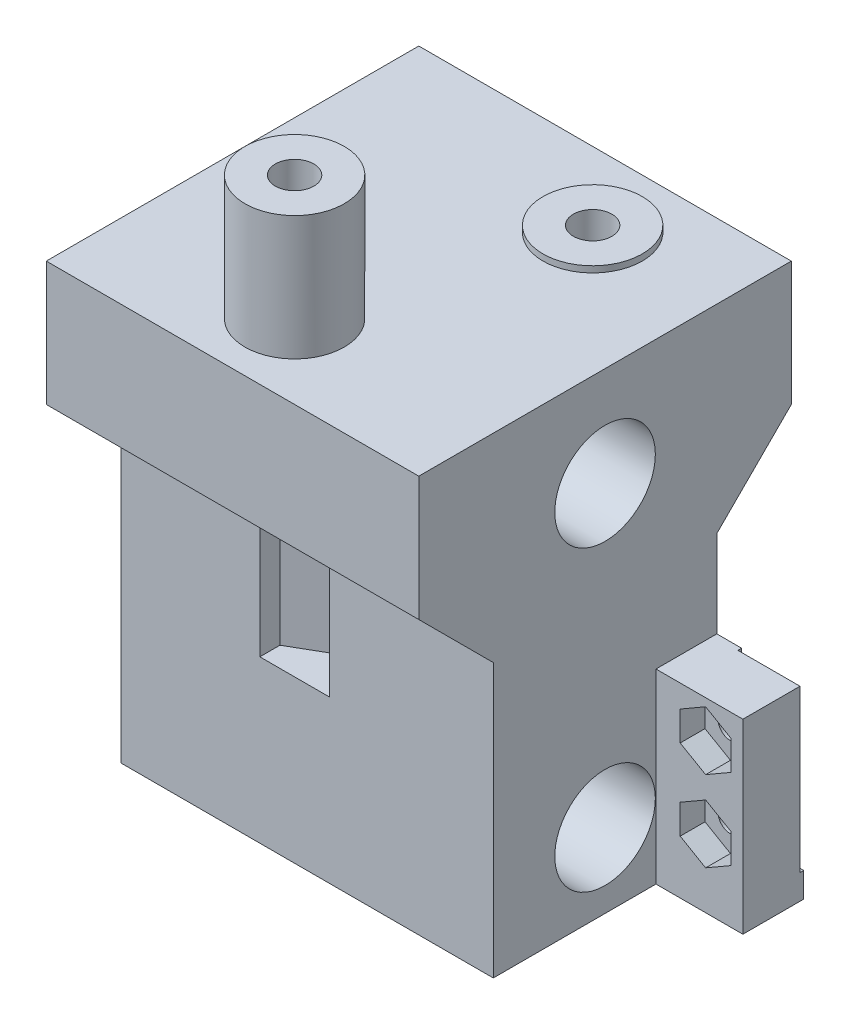
SolidWorks part; units mm, degrees
ref_plane "前视基准面" through (0, 0, 0) normal (0, 0, 1) x (1, 0, 0)
ref_plane "上视基准面" through (0, 0, 0) normal (0, 1, 0) x (1, 0, 0)
ref_plane "右视基准面" through (0, 0, 0) normal (1, 0, 0) x (0, 0, -1)
sketch "草图1" plane through (0, 0, 0) normal (0, 1, 0) x (1, 0, 0)
  line L0 (0, 0) -> (30, 0)
  line L1 (30, 0) -> (30, 30)
  line L2 (30, 30) -> (0, 30)
  line L3 (0, 30) -> (0, 0)
  dimension "D1" = 30
  dimension "D2" = 30
extrude "凸台-拉伸1" add sketch "草图1" along normal blind 38
sketch "草图3" plane through (0, 38, -50) normal (0, -1, 0) x (1, 0, 0)
  line L0 (0, 20) -> (0, 50) construction
  line L3 (30, 20) -> (0, 20) construction
  circle A0 centre (20, 26) radius 4
  dimension "D1" = 8
  dimension "D2" = 6
  dimension "D3" = 20
extrude "凸台-拉伸3" add sketch "草图3" against normal blind 0.5
sketch "草图7" plane through (0, 38, 0) normal (0, -1, 0) x (1, 0, 0)
  line L0 (0, -30) -> (0, 0) construction
  line L2 (0, 0) -> (30, 0) construction
  circle A0 centre (14, -6) radius 4
  point P6 (0, -15)
  dimension "D1" = 8
  dimension "D2" = 14
  dimension "D3" = 6
extrude "凸台-拉伸4" add sketch "草图7" against normal blind 10
ref_plane "基准面1" through (0, 28, 0) normal (0, 1, 0) x (1, 0, 0)
sketch "草图6" plane through (30, 0, 0) normal (1, 0, 0) x (0, 0, -1)
  line L0 (0, 38) -> (0, 0) construction
  line L1 (0, 0) -> (30, 0) construction
  circle A0 centre (15, 6) radius 4.05
  circle A1 centre (15, 30) radius 4.05
  dimension "D4" = 8.1
  dimension "D5" = 8.1
  dimension "D1" = 24
  dimension "D2" = 15
  dimension "D3" = 15
  dimension "D6" = 6
extrude "切除-拉伸3" cut sketch "草图6" against normal through all
sketch "草图9" plane through (0, 28, 0) normal (0, 1, 0) x (1, 0, 0)
  circle A0 centre (14, 6) radius 1.55
  circle A1 centre (20, 24) radius 1.55
  circle A2 centre (14, 6) radius 4 construction
  circle A3 centre (20, 24) radius 4 construction
  dimension "D1" = 3.1
  dimension "D2" = 3.1
extrude "切除-拉伸4" cut sketch "草图9" along normal through all
sketch "草图11" plane through (30, 0, 0) normal (1, 0, 0) x (0, 0, -1)
  line L0 (6, 0) -> (6, 22)
  line L1 (0, 0) -> (30, 0) construction
  line L2 (24, 0) -> (24, 22)
  line L3 (24, 22) -> (30, 28)
  line L4 (16.5, 28) -> (-16.5, 28) construction
  line L5 (30, 38) -> (30, 0) construction
  line L6 (30, 28) -> (30, 0)
  line L7 (30, 0) -> (24, 0)
  line L8 (6, 0) -> (0, 0)
  line L9 (0, 0) -> (0, 28)
  line L10 (0, 38) -> (0, 0) construction
  line L11 (0, 28) -> (6, 22)
  dimension "D1" = 45
  dimension "D2" = 45
  dimension "D3" = 6
  dimension "D4" = 6
extrude "切除-拉伸6" cut sketch "草图11" against normal through all
sketch "草图10" plane through (0, 28, 0) normal (0, 1, 0) x (1, 0, 0)
  line L0 (0, 0) -> (30, 0) construction
  line L1 (16.8, 0) -> (16.8, 7.6166)
  line L2 (16.8, 7.6166) -> (14, 9.2332)
  line L3 (14, 9.2332) -> (11.2, 7.6166)
  line L4 (11.2, 7.6166) -> (11.2, 0)
  line L7 (20, 20.7668) -> (22.8, 22.3834)
  line L8 (22.8, 22.3834) -> (22.8, 30)
  line L11 (17.2, 30) -> (17.2, 22.3834)
  line L12 (17.2, 22.3834) -> (20, 20.7668)
  line L14 (30, 0) -> (30, 30) construction
  line L15 (30, 30) -> (0, 30) construction
  line L16 (0, 30) -> (0, 0) construction
  line L17 (11.2, 4.3834) -> (14, 2.7668) [skipped]
  line L18 (14, 2.7668) -> (16.8, 4.3834) [skipped]
  line L19 (22.8, 25.6166) -> (20, 27.2332) [skipped]
  line L20 (20, 27.2332) -> (17.2, 25.6166) [skipped]
  line L21 (17.2, 30) -> (22.8, 30)
  line L22 (11.2, 0) -> (16.8, 0)
  circle A0 centre (14, 6) radius 2.8 construction
  circle A1 centre (20, 24) radius 2.8 construction
  circle A2 centre (20, 24) radius 1.55 construction
  circle A3 centre (14, 6) radius 1.55 construction
  dimension "D5" = 5.6
  dimension "D6" = 5.6
extrude "切除-拉伸5" cut sketch "草图10" against normal blind 15
sketch "草图12" plane through (30, 0, 0) normal (1, 0, 0) x (0, 0, -1)
  line L0 (19.1, 15) -> (19.1, 0)
  line L2 (19.1, 15) -> (24, 15)
  line L5 (24, 15) -> (24, 0)
  line L7 (24, 22) -> (24, 0) construction
  line L12 (0, 38) -> (0, 28)
  line L14 (0, 28) -> (6, 22)
  line L15 (6, 0) -> (24, 0)
  line L16 (6, 22) -> (6, 0)
  line L17 (24, 0) -> (24, 22)
  line L18 (30, 28) -> (30, 38)
  line L19 (30, 38) -> (0, 38)
  line L23 (19.1, 0) -> (24, 0)
  line L29 (24, 22) -> (30, 28)
  dimension "D2" = 15
  dimension "D3" = 4.9
  dimension "D1" = 0
extrude "凸台-拉伸5" add sketch "草图12" along normal blind 7
sketch "草图13" plane through (0, 0, -24) normal (0, 0, -1) x (-1, 0, 0)
  line L0 (-32, 15) -> (-32, 2)
  line L2 (-32, 2) -> (-37, 2)
  line L4 (-37, 2) -> (-37, 15)
  line L5 (-37, 15) -> (-32, 15)
  dimension "D1" = 5
  dimension "D2" = 13
extrude "切除-拉伸7" cut sketch "草图13" against normal blind 0.3
sketch "草图14" plane through (0, 0, -23.7) normal (0, 0, -1) x (-1, 0, 0)
  line L0 (-37, 15) -> (-37, 2) construction
  line L1 (-32, 15) -> (-37, 15) construction
  circle A0 centre (-34, 12) radius 1
  circle A1 centre (-34, 5.5) radius 1
  dimension "D1" = 2
  dimension "D2" = 2
  dimension "D3" = 3
  dimension "D4" = 3
  dimension "D5" = 3
  dimension "D6" = 6.5
extrude "切除-拉伸8" cut sketch "草图14" against normal through all
sketch "草图15" plane through (0, 0, -19.1) normal (0, 0, 1) x (1, 0, 0)
  line L0 (37, 15) -> (37, 0) construction
  line L1 (36.05, 10.8164) -> (36.05, 13.1836)
  line L2 (36.05, 13.1836) -> (34, 14.3671)
  line L3 (34, 14.3671) -> (31.95, 13.1836)
  line L4 (31.95, 13.1836) -> (31.95, 10.8164)
  line L5 (31.95, 10.8164) -> (34, 9.6329)
  line L6 (34, 9.6329) -> (36.05, 10.8164)
  line L7 (37, 15) -> (37, 0) construction
  line L8 (34, 3.1329) -> (36.05, 4.3164)
  line L9 (36.05, 4.3164) -> (36.05, 6.6836)
  line L10 (36.05, 6.6836) -> (34, 7.8671)
  line L11 (34, 7.8671) -> (31.95, 6.6836)
  line L12 (31.95, 6.6836) -> (31.95, 4.3164)
  line L13 (31.95, 4.3164) -> (34, 3.1329)
  circle A0 centre (34, 12) radius 2.05 construction
  circle A1 centre (34, 5.5) radius 2.05 construction
  dimension "D1" = 4.1
  dimension "D2" = 4.1
extrude "切除-拉伸9" cut sketch "草图15" against normal blind 2
